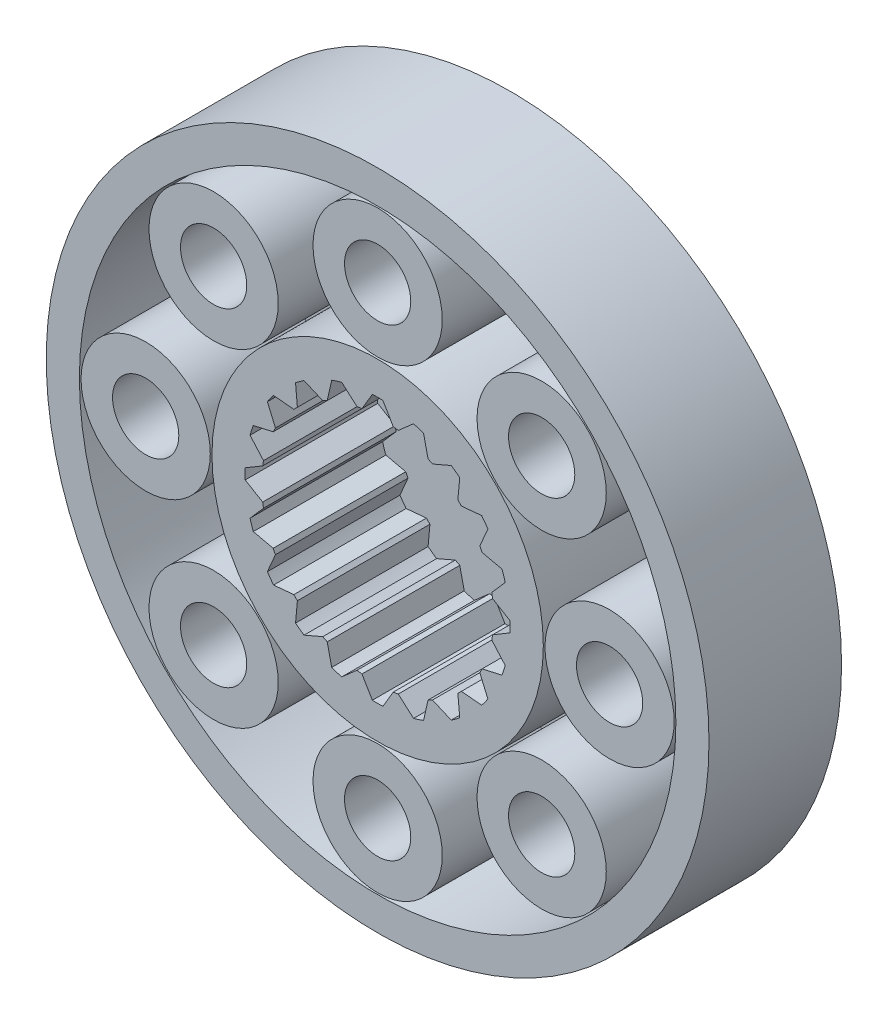
SolidWorks part; units mm, degrees
ref_plane "Front Plane" through (0, 0, 0) normal (0, 0, 1) x (1, 0, 0)
ref_plane "Top Plane" through (0, 0, 0) normal (0, 1, 0) x (1, 0, 0)
ref_plane "Right Plane" through (0, 0, 0) normal (1, 0, 0) x (0, 0, -1)
sketch "Sketch1" plane through (0, 0, 0) normal (0, 0, 1) x (1, 0, 0)
  circle A0 centre (0, 0) radius 10
  dimension "D1" = 20
extrude "Boss-Extrude1" add sketch "Sketch1" along normal blind 4
sketch "Sketch5" plane through (0, 0, 0) normal (0, 0, -1) x (-1, 0, 0)
  circle A0 centre (0, 0) radius 9
  circle A1 centre (0, 0) radius 10 construction
  circle A2 centre (0, 7) radius 1.95
  circle A3 centre (0, 0) radius 5
  circle A4 centre (4.9497, 4.9497) radius 1.95
  circle A5 centre (7, 0) radius 1.95
  circle A6 centre (4.9497, -4.9497) radius 1.95
  circle A7 centre (0, -7) radius 1.95
  circle A8 centre (-4.9497, -4.9497) radius 1.95
  circle A9 centre (-7, 0) radius 1.95
  circle A10 centre (-4.9497, 4.9497) radius 1.95
  point P24 (0, 0)
  dimension "D1" = 1
  dimension "D2" = 3.9
  dimension "D4" = 10
  dimension "D3" = 7
extrude "Cut-Extrude5" cut sketch "Sketch5" against normal up to surface (4 mm away) from offset 0.5 contours A7 A0 A6 A3 | A8 A0 A7 A3 | A9 A0 A8 A3 | A10 A0 A9 A3 | A10 A3 A2 A0 | A4 A0 A2 A3 | A5 A0 A4 A3 | A6 A0 A5 A3 region at (8.9745, 0, 0) up to face at (10, 0, 4) offset against normal yes
sketch "Sketch8" plane through (0, 0, 4) normal (0, 0, 1) x (1, 0, 0)
  circle A0 centre (0, 0) radius 4
  circle A1 centre (0, 7) radius 1
  circle A2 centre (0, 0) radius 5 construction
  circle A3 centre (4.9497, 4.9497) radius 1
  circle A4 centre (7, 0) radius 1
  circle A5 centre (4.9497, -4.9497) radius 1
  circle A6 centre (0, -7) radius 1
  circle A7 centre (-4.9497, -4.9497) radius 1
  circle A8 centre (-7, 0) radius 1
  circle A9 centre (-4.9497, 4.9497) radius 1
  point P24 (0, 0)
  dimension "D1" = 2
  dimension "D2" = 1
extrude "Cut-Extrude7" cut sketch "Sketch8" against normal up to next
sketch "Sketch10" plane through (0, 0, 0) normal (0, 0, -1) x (-1, 0, 0)
  circle A0 centre (0, 0) radius 4.5
  dimension "D1" = 9
extrude "Boss-Extrude12" add sketch "Sketch10" along normal blind 0.2
fillet "Fillet2" radius 0.1 1 edges at (-4.5, 0, -0.2)
sketch "Sketch11" plane through (0, 0, -0.2) normal (0, 0, -1) x (-1, 0, 0)
  circle A0 centre (0, 0) radius 1.5
  dimension "D1" = 3
extrude "Cut-Extrude8" cut sketch "Sketch11" against normal up to next
sketch "Sketch12" plane through (0, 0, 0) normal (0, 0, 1) x (1, 0, 0)
  line L0 (-0.1587, 3.9968) -> (-0.4729, 3.4679)
  line L1 (0, 4) -> (0, 0) construction
  line L2 (0.1587, 3.9968) -> (0.4729, 3.4679)
  line L3 (1.0841, 3.8503) -> (0.6219, 3.4443)
  line L4 (1.3861, 3.7522) -> (1.5214, 3.1521)
  line L5 (2.2209, 3.3268) -> (1.6558, 3.0835)
  line L6 (2.4777, 3.1402) -> (2.4209, 2.5277)
  line L7 (3.1402, 2.4777) -> (2.5277, 2.4209)
  line L8 (3.3268, 2.2209) -> (3.0835, 1.6558)
  line L9 (3.7522, 1.3861) -> (3.1521, 1.5214)
  line L10 (3.8503, 1.0841) -> (3.4443, 0.6219)
  line L11 (3.9968, 0.1587) -> (3.4679, 0.4729)
  line L12 (3.9968, -0.1587) -> (3.4679, -0.4729)
  line L13 (3.8503, -1.0841) -> (3.4443, -0.6219)
  line L14 (3.7522, -1.3861) -> (3.1521, -1.5214)
  line L15 (3.3268, -2.2209) -> (3.0835, -1.6558)
  line L16 (3.1402, -2.4777) -> (2.5277, -2.4209)
  line L17 (2.4777, -3.1402) -> (2.4209, -2.5277)
  line L18 (2.2209, -3.3268) -> (1.6558, -3.0835)
  line L19 (1.3861, -3.7522) -> (1.5214, -3.1521)
  line L20 (1.0841, -3.8503) -> (0.6219, -3.4443)
  line L21 (0.1587, -3.9968) -> (0.4729, -3.4679)
  line L22 (-0.1587, -3.9968) -> (-0.4729, -3.4679)
  line L23 (-1.0841, -3.8503) -> (-0.6219, -3.4443)
  line L24 (-1.3861, -3.7522) -> (-1.5214, -3.1521)
  line L25 (-2.2209, -3.3268) -> (-1.6558, -3.0835)
  line L26 (-2.4777, -3.1402) -> (-2.4209, -2.5277)
  line L27 (-3.1402, -2.4777) -> (-2.5277, -2.4209)
  line L28 (-3.3268, -2.2209) -> (-3.0835, -1.6558)
  line L29 (-3.7522, -1.3861) -> (-3.1521, -1.5214)
  line L30 (-3.8503, -1.0841) -> (-3.4443, -0.6219)
  line L31 (-3.9968, -0.1587) -> (-3.4679, -0.4729)
  line L32 (-3.9968, 0.1587) -> (-3.4679, 0.4729)
  line L33 (-3.8503, 1.0841) -> (-3.4443, 0.6219)
  line L34 (-3.7522, 1.3861) -> (-3.1521, 1.5214)
  line L35 (-3.3268, 2.2209) -> (-3.0835, 1.6558)
  line L36 (-3.1402, 2.4777) -> (-2.5277, 2.4209)
  line L37 (-2.4777, 3.1402) -> (-2.4209, 2.5277)
  line L38 (-2.2209, 3.3268) -> (-1.6558, 3.0835)
  line L39 (-1.3861, 3.7522) -> (-1.5214, 3.1521)
  line L40 (-1.0841, 3.8503) -> (-0.6219, 3.4443)
  arc A0 (1.0841, 3.8503) -> (0.1587, 3.9968) centre (0, 0) ccw
  arc A1 (0.6219, 3.4443) -> (0.4729, 3.4679) centre (0, 0) ccw
  circle A2 centre (0, 0) radius 4 construction
  circle A3 centre (0, 0) radius 4 construction
  arc A4 (2.2209, 3.3268) -> (1.3861, 3.7522) centre (0, 0) ccw
  arc A5 (1.6558, 3.0835) -> (1.5214, 3.1521) centre (0, 0) ccw
  arc A6 (3.1402, 2.4777) -> (2.4777, 3.1402) centre (0, 0) ccw
  arc A7 (2.5277, 2.4209) -> (2.4209, 2.5277) centre (0, 0) ccw
  arc A8 (3.7522, 1.3861) -> (3.3268, 2.2209) centre (0, 0) ccw
  arc A9 (3.1521, 1.5214) -> (3.0835, 1.6558) centre (0, 0) ccw
  arc A10 (3.9968, 0.1587) -> (3.8503, 1.0841) centre (0, 0) ccw
  arc A11 (3.4679, 0.4729) -> (3.4443, 0.6219) centre (0, 0) ccw
  arc A12 (3.8503, -1.0841) -> (3.9968, -0.1587) centre (0, 0) ccw
  arc A13 (3.4443, -0.6219) -> (3.4679, -0.4729) centre (0, 0) ccw
  arc A14 (3.3268, -2.2209) -> (3.7522, -1.3861) centre (0, 0) ccw
  arc A15 (3.0835, -1.6558) -> (3.1521, -1.5214) centre (0, 0) ccw
  arc A16 (2.4777, -3.1402) -> (3.1402, -2.4777) centre (0, 0) ccw
  arc A17 (2.4209, -2.5277) -> (2.5277, -2.4209) centre (0, 0) ccw
  arc A18 (1.5214, -3.1521) -> (1.6558, -3.0835) centre (0, 0) ccw
  arc A19 (1.3861, -3.7522) -> (2.2209, -3.3268) centre (0, 0) ccw
  arc A20 (0.4729, -3.4679) -> (0.6219, -3.4443) centre (0, 0) ccw
  arc A21 (0.1587, -3.9968) -> (1.0841, -3.8503) centre (0, 0) ccw
  arc A22 (-0.6219, -3.4443) -> (-0.4729, -3.4679) centre (0, 0) ccw
  arc A23 (-1.0841, -3.8503) -> (-0.1587, -3.9968) centre (0, 0) ccw
  arc A24 (-1.6558, -3.0835) -> (-1.5214, -3.1521) centre (0, 0) ccw
  arc A25 (-2.2209, -3.3268) -> (-1.3861, -3.7522) centre (0, 0) ccw
  arc A26 (-2.5277, -2.4209) -> (-2.4209, -2.5277) centre (0, 0) ccw
  arc A27 (-3.1402, -2.4777) -> (-2.4777, -3.1402) centre (0, 0) ccw
  arc A28 (-3.1521, -1.5214) -> (-3.0835, -1.6558) centre (0, 0) ccw
  arc A29 (-3.7522, -1.3861) -> (-3.3268, -2.2209) centre (0, 0) ccw
  arc A30 (-3.4679, -0.4729) -> (-3.4443, -0.6219) centre (0, 0) ccw
  arc A31 (-3.9968, -0.1587) -> (-3.8503, -1.0841) centre (0, 0) ccw
  arc A32 (-3.4443, 0.6219) -> (-3.4679, 0.4729) centre (0, 0) ccw
  arc A33 (-3.8503, 1.0841) -> (-3.9968, 0.1587) centre (0, 0) ccw
  arc A34 (-3.0835, 1.6558) -> (-3.1521, 1.5214) centre (0, 0) ccw
  arc A35 (-3.3268, 2.2209) -> (-3.7522, 1.3861) centre (0, 0) ccw
  arc A36 (-2.4209, 2.5277) -> (-2.5277, 2.4209) centre (0, 0) ccw
  arc A37 (-2.4777, 3.1402) -> (-3.1402, 2.4777) centre (0, 0) ccw
  arc A38 (-1.5214, 3.1521) -> (-1.6558, 3.0835) centre (0, 0) ccw
  arc A39 (-1.3861, 3.7522) -> (-2.2209, 3.3268) centre (0, 0) ccw
  arc A40 (-0.4729, 3.4679) -> (-0.6219, 3.4443) centre (0, 0) ccw
  arc A41 (-0.1587, 3.9968) -> (-1.0841, 3.8503) centre (0, 0) ccw
  point P91 (0, 0)
  dimension "D1" = 0.5
  dimension "D2" = 20
extrude "Boss-Extrude13" add sketch "Sketch12" along normal blind 4
